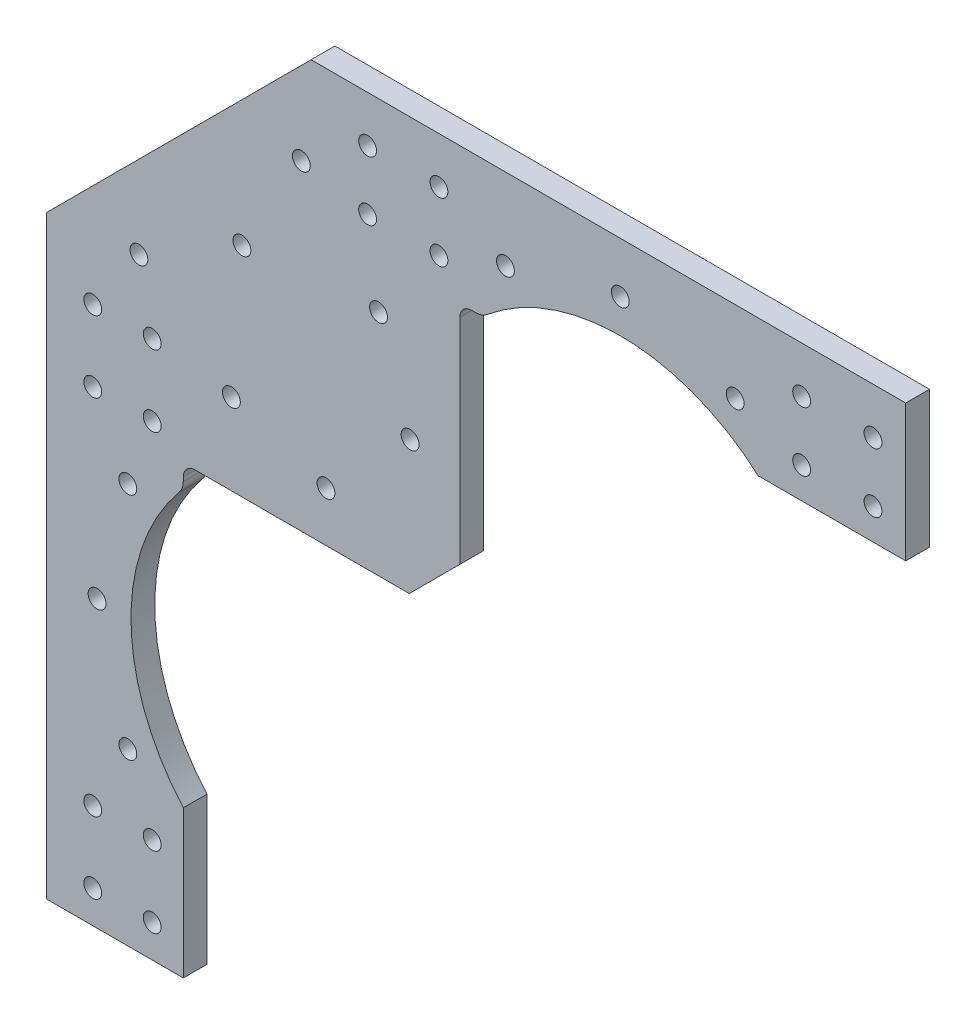
SolidWorks part; units mm, degrees
ref_plane "Front Plane" through (0, 0, 0) normal (0, 0, 1) x (1, 0, 0)
ref_plane "Top Plane" through (0, 0, 0) normal (0, 1, 0) x (1, 0, 0)
ref_plane "Right Plane" through (0, 0, 0) normal (1, 0, 0) x (0, 0, -1)
sketch "Sketch1" plane through (0, 0, 0) normal (0, 0, 1) x (1, 0, 0)
  line L0 (0, 0) -> (0, 73.5) construction
  line L1 (-96.5, -48) -> (-73.5, -48)
  line L2 (-96.5, -48) -> (-96.5, 52)
  line L4 (-73.5, -48) -> (-73.5, 27) construction
  line L5 (-52, 96.5) -> (48, 96.5)
  line L7 (-27, 73.5) -> (48, 73.5) construction
  line L8 (48, 96.5) -> (48, 73.5)
  line L9 (0, 0) -> (-73.5, 0) construction
  line L10 (-27, 73.5) -> (-73.5, 27) construction
  line L11 (-73.5, 73.5) -> (-27, 73.5) construction
  line L12 (-73.5, 27) -> (-73.5, 73.5) construction
  line L13 (-52, 96.5) -> (-96.5, 52)
  line L14 (-96.5, 96.5) -> (-52, 96.5) construction
  line L15 (-96.5, 52) -> (-96.5, 96.5) construction
  line L16 (-24.3179, 73.5) -> (-25, 73.5)
  line L17 (23.2069, 73.5) -> (48, 73.5)
  line L18 (-73.5, 25) -> (-73.5, 24.3179)
  line L19 (-73.5, -48) -> (-73.5, -23.2069)
  line L20 (-73.5, 23.2069) -> (-73.5, -23.2069) construction
  line L21 (-23.2069, 73.5) -> (23.2069, 73.5) construction
  line L22 (-71.5, 27) -> (-35.4853, 27)
  line L23 (-27, 35.4853) -> (-27, 71.5)
  line L24 (-35.4853, 27) -> (-27, 35.4853)
  line L25 (-25, 73.5) -> (-27, 73.5) construction
  line L26 (-27, 71.5) -> (-27, 73.5) construction
  line L27 (-73.5, 27) -> (-73.5, 25) construction
  line L28 (-73.5, 27) -> (-71.5, 27) construction
  line L29 (-23.2069, 73.5) -> (-24.3179, 73.5) construction
  line L30 (-73.5, 24.3179) -> (-73.5, 23.2069) construction
  arc A0 (23.2069, 73.5) -> (-22.3981, 74.1947) centre (0, 47.3) ccw
  arc A1 (-74.1947, 22.3981) -> (-73.5, -23.2069) centre (-47.3, 0) ccw
  arc A2 (-25, 73.5) -> (-27, 71.5) centre (-25, 71.5) ccw
  arc A3 (-71.5, 27) -> (-73.5, 25) centre (-71.5, 25) ccw
  arc A4 (-24.3179, 73.5) -> (-22.3981, 74.1947) centre (-24.3179, 76.5) ccw
  arc A5 (-22.3981, 74.1947) -> (-23.2069, 73.5) centre (0, 47.3) ccw construction
  arc A6 (-73.5, 24.3179) -> (-74.1947, 22.3981) centre (-76.5, 24.3179) cw
  arc A7 (-73.5, 23.2069) -> (-74.1947, 22.3981) centre (-47.3, 0) ccw construction
  dimension "D6" = 35
  dimension "D10" = 2
  dimension "D11" = 3
  dimension "D1" = 135
  dimension "D2" = 23
  dimension "D3" = 73.5
  dimension "D4" = 48
  dimension "D8" = 27
  dimension "D9" = 12
  dimension "D5" = 100
  dimension "D7" = 26.2
extrude "Boss-Extrude1" add sketch "Sketch1" along normal blind 4
ref_axis "Axis1" through (0, 0, -0.2) along (0, 0, 1)
sketch "Sketch3" plane through (0, 0, 4) normal (0, 0, 1) x (1, 0, 0)
  line L1 (30.5, 88.7259) -> (30.5, 78.7259) construction
  line L2 (30.5, 88.7259) -> (42.5, 88.7259) construction
  line L3 (42.5, 88.7259) -> (42.5, 78.7259) construction
  line L4 (30.5, 78.7259) -> (42.5, 78.7259) construction
  line L16 (-30.5, 78.7259) -> (0, 78.7259) construction
  line L17 (0, 78.7259) -> (0, 0) construction
  line L18 (0, 78.7259) -> (30.5, 78.7259) construction
  line L19 (-78.7259, 0) -> (0, 0) construction
  line L20 (-78.7259, -30.5) -> (-78.7259, 0) construction
  line L21 (-78.7259, 0) -> (-78.7259, 30.5) construction
  line L30 (-42.5, 88.7259) -> (-42.5, 78.7259) construction
  line L31 (-42.5, 88.7259) -> (-30.5, 88.7259) construction
  line L32 (-30.5, 88.7259) -> (-30.5, 78.7259) construction
  line L33 (-42.5, 78.7259) -> (-30.5, 78.7259) construction
  line L34 (-88.7259, 42.5) -> (-88.7259, 30.5) construction
  line L35 (-88.7259, 42.5) -> (-78.7259, 42.5) construction
  line L36 (-78.7259, 42.5) -> (-78.7259, 30.5) construction
  line L37 (-88.7259, 30.5) -> (-78.7259, 30.5) construction
  line L38 (-88.7259, -30.5) -> (-88.7259, -42.5) construction
  line L39 (-88.7259, -30.5) -> (-78.7259, -30.5) construction
  line L40 (-78.7259, -30.5) -> (-78.7259, -42.5) construction
  line L41 (-88.7259, -42.5) -> (-78.7259, -42.5) construction
  circle A0 centre (30.5, 78.7259) radius 1.5
  circle A1 centre (30.5, 88.7259) radius 1.5
  circle A2 centre (42.5, 88.7259) radius 1.5
  circle A3 centre (42.5, 78.7259) radius 1.5
  circle A24 centre (-42.5, 78.7259) radius 1.5
  circle A25 centre (-42.5, 88.7259) radius 1.5
  circle A26 centre (-30.5, 88.7259) radius 1.5
  circle A27 centre (-30.5, 78.7259) radius 1.5
  circle A28 centre (-88.7259, 30.5) radius 1.5
  circle A29 centre (-88.7259, 42.5) radius 1.5
  circle A30 centre (-78.7259, 42.5) radius 1.5
  circle A31 centre (-78.7259, 30.5) radius 1.5
  circle A32 centre (-88.7259, -42.5) radius 1.5
  circle A33 centre (-88.7259, -30.5) radius 1.5
  circle A34 centre (-78.7259, -30.5) radius 1.5
  circle A35 centre (-78.7259, -42.5) radius 1.5
  dimension "D1" = 3
  dimension "D8" = 30.5
  dimension "D2" = 12
  dimension "D6" = 10
  dimension "D3" = 78.7259
extrude "Cut-Extrude1" cut sketch "Sketch3" against normal blind 10
sketch "Sketch4" plane through (0, 0, 4) normal (0, 0, 1) x (1, 0, 0)
  line L0 (0, 0) -> (0, 88) construction
  line L1 (0, 0) -> (-63.6396, 63.6396) construction
  line L2 (0, 0) -> (-88, 0) construction
  line L3 (-82.8236, 19.3185) -> (-88, 0) construction
  line L4 (-88, 0) -> (-82.8236, -19.3185) construction
  line L5 (-80.9601, 53.6396) -> (-63.6396, 63.6396) construction
  line L6 (-63.6396, 63.6396) -> (-83.2677, 83.2677) construction
  line L7 (-19.3185, 82.8236) -> (0, 88) construction
  line L8 (-65.4074, 40.6586) -> (-40.6586, 65.4074) construction
  line L9 (-35.3553, 49.4975) -> (-49.4975, 35.3553) construction
  line L10 (-73.5, -48) -> (-73.5, -23.2069) construction
  line L11 (-35.4853, 27) -> (-27, 35.4853) construction
  circle A0 centre (-88, 0) radius 1.5
  circle A1 centre (-63.6396, 63.6396) radius 1.5
  circle A2 centre (0, 88) radius 1.5
  circle A3 centre (-80.9601, 53.6396) radius 1.5
  circle A4 centre (-53.6396, 80.9601) radius 1.5
  circle A5 centre (19.3185, 82.8236) radius 1.5
  circle A6 centre (-19.3185, 82.8236) radius 1.5
  circle A7 centre (-82.8236, 19.3185) radius 1.5
  circle A8 centre (-82.8236, -19.3185) radius 1.5
  circle A9 centre (-40.6586, 65.4074) radius 1.5
  circle A10 centre (-65.4074, 40.6586) radius 1.5
  circle A11 centre (-49.4975, 35.3553) radius 1.5
  circle A12 centre (-35.3553, 49.4975) radius 1.5
  dimension "D2" = 3
  dimension "D1" = 45
  dimension "D3" = 14.5
  dimension "D4" = 75
  dimension "D5" = 20
  dimension "D6" = 45.8162
  dimension "D7" = 75
  dimension "D8" = 75
  dimension "D9" = 35
  dimension "D10" = 20
  dimension "D11" = 15
  dimension "D12" = 15
extrude "Cut-Extrude2" cut sketch "Sketch4" against normal through all
equation "\"EyeDiameter\" = 35"
equation "\"BasePlaneDistance\" = \"EyeDiameter\"/2+19.84"
equation "\"EyeClearance\" = 2"
equation "\"L2Thickness\" = 8"
equation "\"L2_ID\" = 20"
equation "\"Offset\"= - 2"
equation "\"D3@Sketch1\"=\"BasePlaneDistance\" + 38.16 +\"Offset\""
equation "\"D3@Sketch3\"=\"BasePlaneDistance\" - 37.34+78.72592343"
equation "\"D7@Sketch1\"=24.20 - \"Offset\""
equation "\"D2@Sketch1\"=25.00 + \"Offset\""
